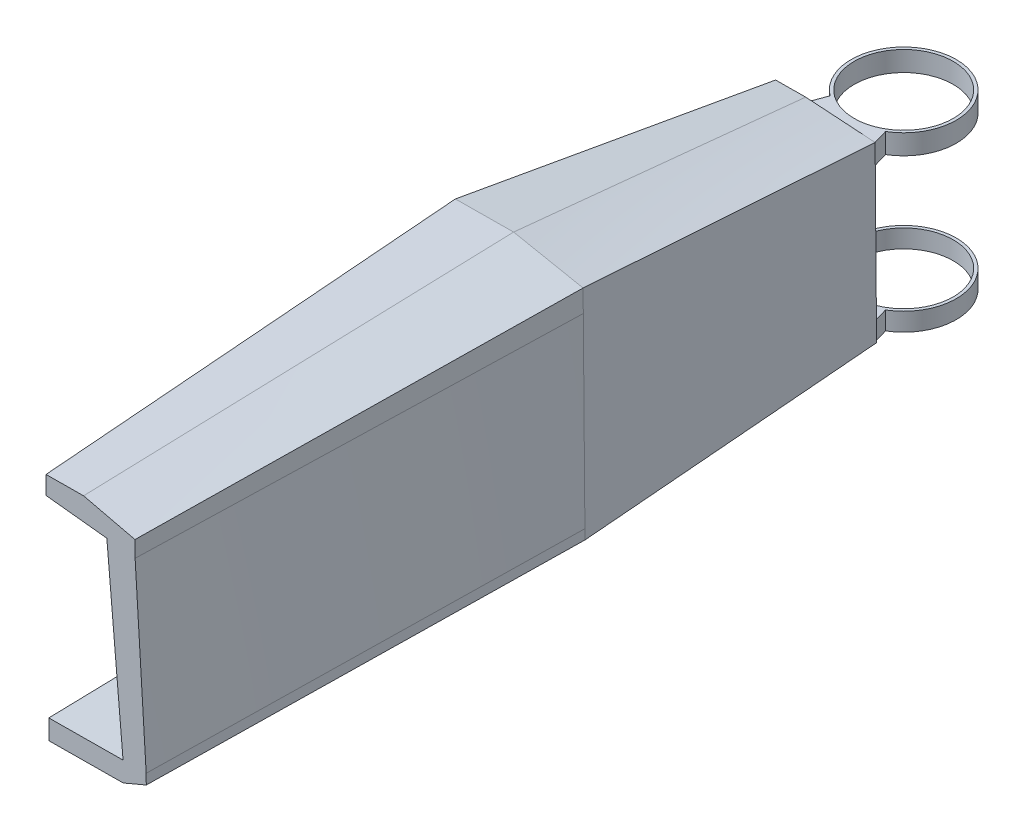
SolidWorks part; units mm, degrees
ref_plane "Front Plane" through (0, 0, 0) normal (0, 0, 1) x (1, 0, 0)
ref_plane "Top Plane" through (0, 0, 0) normal (0, 1, 0) x (1, 0, 0)
ref_plane "Right Plane" through (0, 0, 0) normal (1, 0, 0) x (0, 0, -1)
ref_plane "Plane1" through (0, 0, 238.8713) normal (0, 0, 1) x (1, 0, 0)
ref_plane "Plane2" through (0, 0, 123.4214) normal (0, 0, 1) x (1, 0, 0)
ref_plane "Plane3" through (0, 0, 44.3116) normal (0, 0, 1) x (1, 0, 0)
sketch "Sketch1" plane through (0, 0, 238.8713) normal (0, 0, 1) x (1, 0, 0)
  line L0 (117.4493, 305.1012) -> (133.7996, 303.3144)
  line L1 (117.4493, 305.1012) -> (117.4067, 310.0065)
  line L2 (117.4067, 310.0065) -> (127.5319, 310.0875)
  line L3 (127.5319, 310.0875) -> (141.3761, 306.8036)
  line L4 (141.3761, 306.8036) -> (141.4142, 302.4368)
  line L5 (141.4142, 302.4368) -> (144.3985, 253.7841)
  line L6 (144.3985, 253.7841) -> (144.4224, 251.0419)
  line L7 (144.4224, 251.0419) -> (138.2151, 248.4171)
  line L8 (138.2151, 248.4171) -> (118.2101, 248.2571)
  line L9 (118.2101, 248.2571) -> (118.1636, 253.574)
  line L10 (118.1636, 253.574) -> (138.1689, 253.7343)
  line L11 (138.1689, 253.7343) -> (133.7996, 303.3144)
sketch "Sketch2" plane through (0, 0, 123.4214) normal (0, 0, 1) x (1, 0, 0)
  line L0 (112.2482, 313.9803) -> (127.9439, 314.1061)
  line L1 (127.9439, 314.1061) -> (146.6654, 310.4142)
  line L2 (146.6654, 310.4142) -> (146.7173, 304.4883)
  line L3 (146.7173, 304.4883) -> (147.1534, 254.4976)
  line L4 (147.1534, 254.4976) -> (147.1762, 251.8796)
  line L5 (147.1762, 251.8796) -> (136.0554, 248.8781)
  line L6 (136.0554, 248.8781) -> (116.0501, 248.7178)
  line L7 (116.0501, 248.7178) -> (116.0021, 254.2479)
  line L8 (112.2482, 313.9803) -> (112.3051, 307.4449)
  line L9 (116.0021, 254.2479) -> (136.0071, 254.4082)
  line L10 (136.0071, 254.4082) -> (131.2134, 307.5963)
  line L11 (131.2134, 307.5963) -> (112.3051, 307.4449)
sketch "Sketch3" plane through (0, 0, 44.3116) normal (0, 0, 1) x (1, 0, 0)
  line L0 (119.4778, 299.1543) -> (119.4199, 305.7695)
  line L1 (119.4199, 305.7695) -> (127.5263, 305.8343)
  line L2 (127.5263, 305.8343) -> (146.2263, 304.607)
  line L3 (146.2263, 304.607) -> (146.272, 299.369)
  line L4 (146.272, 299.369) -> (146.5882, 263.1191)
  line L5 (146.5882, 263.1191) -> (146.6322, 258.0739)
  line L6 (146.6322, 258.0739) -> (127.9555, 256.6276)
  line L7 (127.9555, 256.6276) -> (121.5192, 256.5761)
  line L8 (121.5192, 256.5761) -> (121.4638, 262.9179)
  line L9 (121.4638, 262.9179) -> (127.9002, 262.9695)
  line L10 (127.9002, 262.9695) -> (127.5839, 299.2191)
  line L11 (127.5839, 299.2191) -> (119.4778, 299.1543)
loft "Loft1" add profiles "Sketch1", "Sketch2" start constraint default connector at (141.3761, 306.8036, 238.8713) connector at (146.6654, 310.4142, 123.4214)
loft "Loft2" add profiles "Sketch2<3>", "Sketch3" connector at (112.3051, 307.4449, 123.4214) connector at (119.4778, 299.1543, 44.3116)
sketch "Sketch2<3>" plane through (0, 0, 123.4214) normal (0, 0, 1) x (1, 0, 0) same geometry as "Sketch2"
ref_plane "Plane4" through (0, 299.2191, 0) normal (0, 1, 0) x (1, 0, 0)
sketch "Sketch4" plane through (0, 299.2191, 0) normal (0, 1, 0) x (1, 0, 0)
  line L0 (146.2263, -44.3116) -> (145.0785, -40.3616)
  line L1 (127.5263, -44.3116) -> (129.2769, -39.4965)
  line L2 (127.5263, -44.3116) -> (146.2263, -44.3116)
  arc A0 (129.2769, -39.4965) -> (145.0785, -40.3616) centre (137.8202, -28.1929) cw
  circle A1 centre (137.8202, -28.1929) radius 13.3394
  point P6 (138.5921, -14.0449)
  point P8 (149.5687, -34.5105)
extrude "Boss-Extrude1" add sketch "Sketch4" along normal up to vertex (5.3878 mm away) up to point (146.2263, 304.607, 44.3116)
extrude "Boss-Extrude2" add sketch "Sketch4<2>" against normal up to vertex (41.1452 mm away) from vertex up to point (146.6322, 258.0739, 44.3116) starting at point (127.9002, 262.9695, 44.3116)
sketch "Sketch4<2>" plane through (0, 299.2191, 0) normal (0, 1, 0) x (1, 0, 0) same geometry as "Sketch4"
move or copy body "Body-Move/Copy1" [suppressed] bodies to move or copy 104
